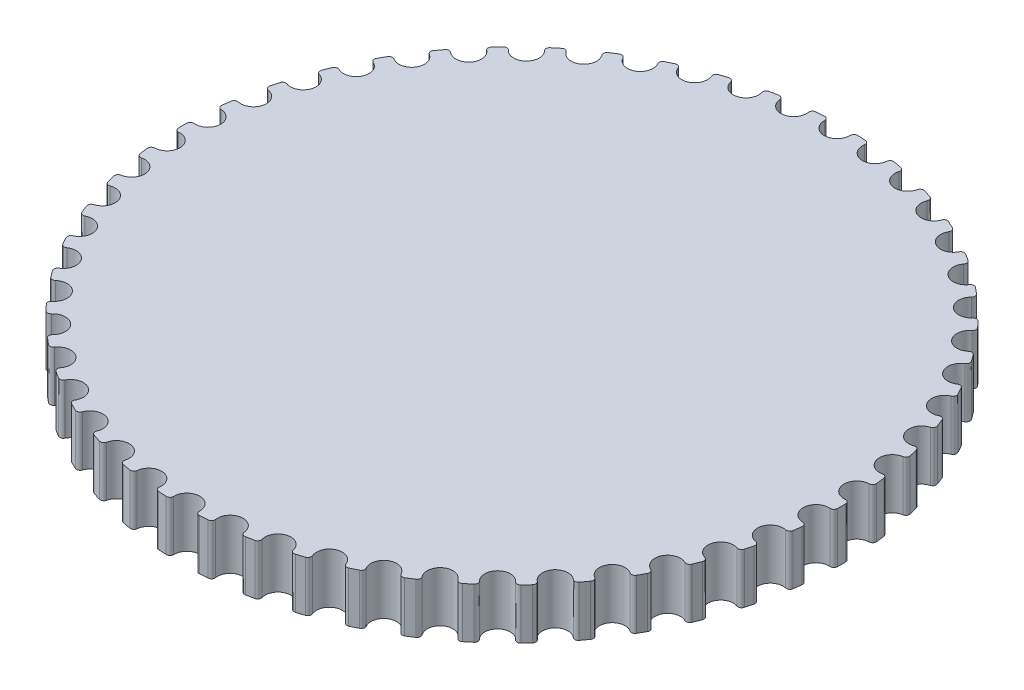
SolidWorks part; units mm, degrees
ref_plane "Front Plane" through (0, 0, 0) normal (0, 0, 1) x (1, 0, 0)
ref_plane "Top Plane" through (0, 0, 0) normal (0, 1, 0) x (1, 0, 0)
ref_plane "Right Plane" through (0, 0, 0) normal (1, 0, 0) x (0, 0, -1)
sketch "Sketch1" plane through (0, 0, 0) normal (0, 1, 0) x (1, 0, 0)
  line L0 (0, 0) -> (0, 39.2175) construction
  line L1 (0, 0) -> (4.8482, 38.3775) construction
  circle A0 centre (0, 0) radius 39.2175 construction
  circle A1 centre (0, 0) radius 37.1575 construction
  circle A2 centre (0, 38.6825) radius 1.525 construction
  circle A5 centre (4.8482, 38.3775) radius 1.525 construction
  arc A6 (0, 37.1575) -> (1.5244, 38.726) centre (0, 38.6825) ccw
  arc A7 (1.5244, 38.726) -> (1.9759, 39.1677) centre (1.9542, 38.7382) cw
  arc A8 (2.9487, 39.1065) -> (3.3413, 38.6117) centre (2.9164, 38.6777) cw
  arc A9 (4.6571, 36.8645) -> (3.3413, 38.6117) centre (4.8482, 38.3775) cw
  arc A10 (1.9759, 39.1677) -> (2.9487, 39.1065) centre (0, 0) cw
  arc A11 (0, 37.1575) -> (4.6571, 36.8645) centre (0, 0) ccw
  point P8 (0, 37.1575)
  point P10 (0, 37.1575)
  point P19 (2.9164, 39.1089)
  point P20 (3.3413, 38.6117)
  point P21 (4.6571, 36.8645)
  point P22 (1.9542, 39.2175)
  point P23 (0, 0)
  point P24 (3.3413, 38.6117)
  point P25 (4.6571, 36.8645)
  point P26 (4.6571, 36.8645)
  dimension "D1" = 78.435
  dimension "D3" = 3.05
  dimension "D4" = 0.43
  dimension "D2" = 2.06
  dimension "D5" = 7.2
extrude "Boss-Extrude1" add sketch "Sketch1" along normal mid plane 6
ref_axis "Axis1" through (0, 3.3, 0) along (0, -1, 0)
pattern_circular "CirPattern1" count 50 over 360 about axis through (0, 3.3, 0) along (0, -1, 0) of "Boss-Extrude1"
equation "\"TEETH_NUM\"= 50"
equation "\"TOOTH_PITCH\"= 5mm"
equation "\"PITCH_LINE_OFFSET\"= .5715mm"
equation "\"DIAMETER_PER_GROOVE\"= 1.59156mm"
equation "\"PITCH_DIAMETER\"= \"TEETH_NUM\" * \"DIAMETER_PER_GROOVE\""
equation "\"OUTSIDE_DIAMETER\" = \"PITCH_DIAMETER\" - \"PITCH_LINE_OFFSET\" * 2"
equation "\"D1@Sketch1\"=\"OUTSIDE_DIAMETER\""
equation "\"TOOTH_HEIGHT\"= 2.06mm"
equation "\"D2@Sketch1\"=\"TOOTH_HEIGHT\""
equation "\"TOOTH_DIAMETER\"= 3.05mm"
equation "\"INTERNAL_RADIUS\"= .43mm"
equation "\"D3@Sketch1\"=\"TOOTH_DIAMETER\""
equation "\"D5@Sketch1\"=360 / \"TEETH_NUM\""
equation "\"D4@Sketch1\"=\"INTERNAL_RADIUS\""
equation "\"D1@CirPattern1\"=\"TEETH_NUM\""
